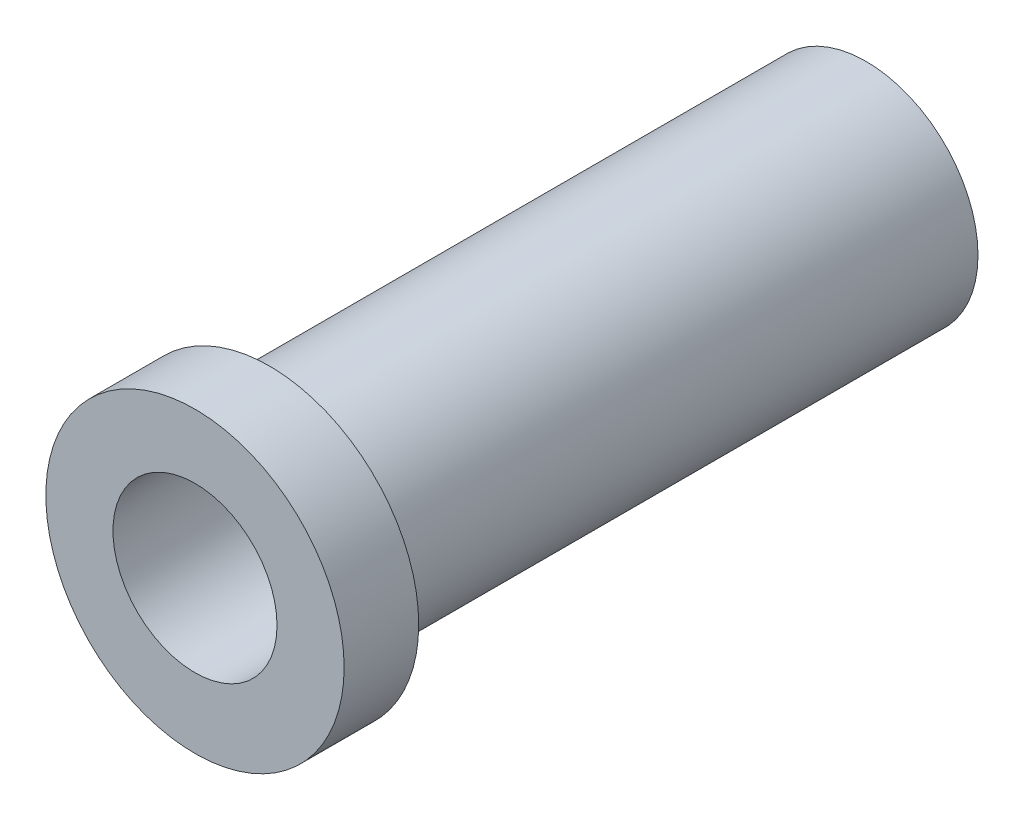
SolidWorks part; units mm, degrees
ref_plane "Front Plane" through (0, 0, 0) normal (0, 0, 1) x (1, 0, 0)
ref_plane "Top Plane" through (0, 0, 0) normal (0, 1, 0) x (1, 0, 0)
ref_plane "Right Plane" through (0, 0, 0) normal (1, 0, 0) x (0, 0, -1)
sketch "Sketch1" plane through (0, 0, 0) normal (0, 0, 1) x (1, 0, 0)
  circle A0 centre (0, 0) radius 5.5
  circle A1 centre (0, 0) radius 7.5
  circle A2 centre (0, -0.1909) radius 10
  dimension "D1" = 11
  dimension "D2" = 15
  dimension "D3" = 20
extrude "Boss-Extrude1" add sketch "Sketch1" against normal blind 40 contours A1 A0 region at (-7.2879, 0, 0)
extrude "Boss-Extrude2" add sketch "Sketch1<3>" along normal blind 5 contours A2 A1 | A1 A0 region at (-7.2879, 0, 0) region at (-9.7172, -0.1909, 0)
sketch "Sketch1<3>" plane through (0, 0, 0) normal (0, 0, 1) x (1, 0, 0) same geometry as "Sketch1"
